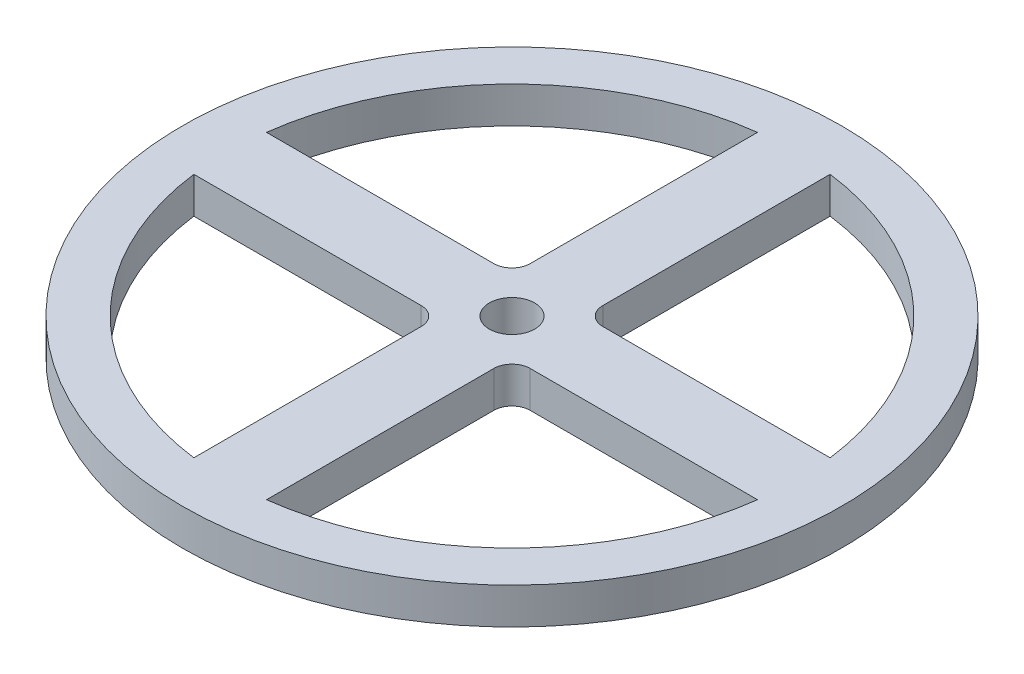
SolidWorks part; units mm, degrees
ref_plane "Front Plane" through (0, 0, 0) normal (0, 0, 1) x (1, 0, 0)
ref_plane "Top Plane" through (0, 0, 0) normal (0, 1, 0) x (1, 0, 0)
ref_plane "Right Plane" through (0, 0, 0) normal (1, 0, 0) x (0, 0, -1)
sketch "Sketch1" plane through (0, 0, 0) normal (0, 1, 0) x (1, 0, 0)
  line L0 (-43.2051, 0) -> (60.4147, 0) construction
  line L1 (0, 48.3176) -> (0, -50.4298) construction
  line L2 (-31.0434, -4) -> (-6, -4)
  line L3 (-4, 31.0434) -> (-4, 6)
  line L4 (-31.0434, 4) -> (-6, 4)
  line L5 (4, 31.0434) -> (4, 6)
  line L6 (-4, -6) -> (-4, -31.0434)
  line L7 (-4, 48.3176) -> (-4, -50.4298) construction
  line L8 (4, 48.3176) -> (4, -50.4298) construction
  line L9 (-43.2051, 4) -> (60.4147, 4) construction
  line L10 (-43.2051, -4) -> (60.4147, -4) construction
  line L11 (6, 4) -> (31.0434, 4)
  line L12 (6, -4) -> (31.0434, -4)
  line L13 (4, -6) -> (4, -31.0434)
  circle A0 centre (0, 0) radius 36.3
  circle A1 centre (0, 0) radius 2.5
  arc A2 (-31.0434, -4) -> (-4, -31.0434) centre (0, 0) ccw
  arc A5 (-6, -4) -> (-4, -6) centre (-6, -6) cw
  arc A6 (-6, 4) -> (-4, 6) centre (-6, 6) ccw
  arc A7 (4, 6) -> (6, 4) centre (6, 6) ccw
  arc A9 (6, -4) -> (4, -6) centre (6, -6) ccw
  arc A10 (-4, 31.0434) -> (-31.0434, 4) centre (0, 0) ccw
  circle A11 centre (0, 0) radius 31.3 construction
  arc A12 (31.0434, 4) -> (4, 31.0434) centre (0, 0) ccw
  arc A13 (4, -31.0434) -> (31.0434, -4) centre (0, 0) ccw
  point P38 (29.9323, 9.1512)
  dimension "D1" = 72.6
  dimension "D2" = 5
  dimension "D4" = 2
  dimension "D7" = 2
  dimension "D8" = 2
  dimension "D9" = 2
  dimension "D3" = 5
  dimension "D5" = 4
  dimension "D6" = 4
extrude "Boss-Extrude1" add sketch "Sketch1" along normal blind 4 contours A0 A13 L13 A9 L12 A12 L11 A7 L5 A10 L3 A6 L4 A1 L2 A5 L6 A2 region at (-35.2733, 0, 0)
